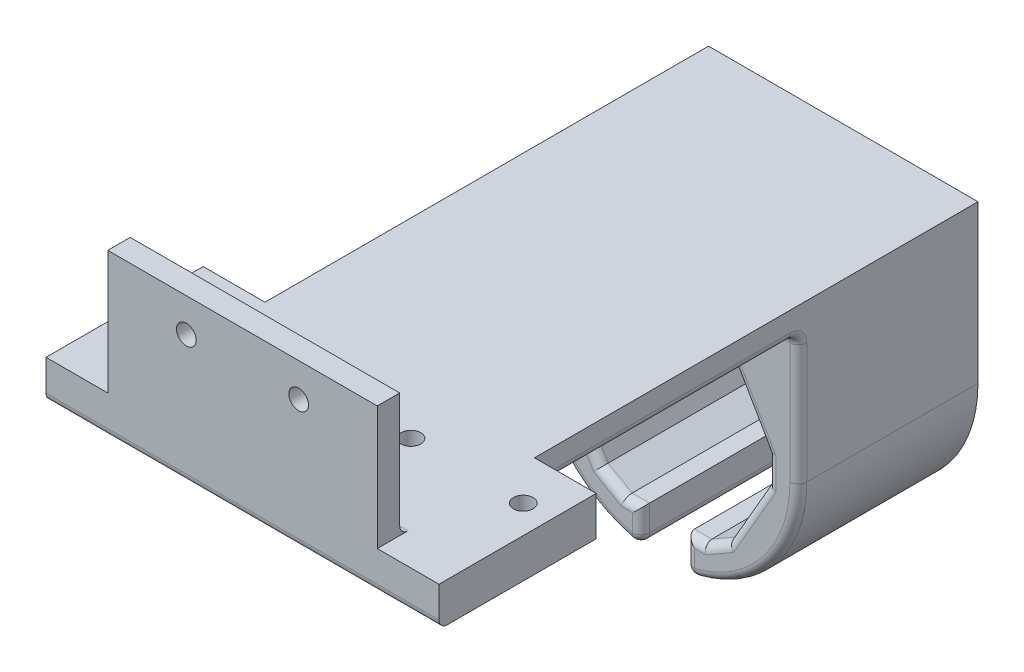
SolidWorks part; units mm, degrees
ref_plane "Front Plane" through (0, 0, 0) normal (1, 0, 0) x (0, 1, 0)
ref_plane "Top Plane" through (0, 0, 0) normal (0, 0, 1) x (0, 1, 0)
ref_plane "Right Plane" through (0, 0, 0) normal (0, 1, 0) x (-1, 0, 0)
sketch "Sketch1" plane through (0, 0, 0) normal (0, 0, 1) x (0, 1, 0)
  circle A0 centre (0, 0) radius 24
  dimension "D1" = 48
extrude "Boss-Extrude2" add sketch "Sketch1" along normal blind 32
sketch "Sketch2" plane through (0, 0, 32) normal (0, 0, 1) x (1, 0, 0)
  line L0 (0, 0) -> (-19.9053, 0) construction
  line L1 (7.1, 17.2385) -> (-7.0999, 17.2385)
  line L2 (-11.379, 14.768) -> (-18.4789, 2.4705)
  line L3 (-18.4789, -2.4705) -> (-11.379, -14.768)
  line L4 (-7.0999, -17.2385) -> (7.1, -17.2385)
  line L5 (11.379, -14.768) -> (18.479, -2.4705)
  line L6 (18.479, 2.4705) -> (11.379, 14.768)
  line L7 (-7.0999, 17.2385) -> (-11.379, 14.768)
  line L8 (11.379, 14.768) -> (7.1, 17.2385)
  line L9 (18.479, -2.4705) -> (18.479, 2.4705)
  line L10 (7.1, -17.2385) -> (11.379, -14.768)
  line L11 (-11.379, -14.768) -> (-7.0999, -17.2385)
  line L12 (-18.4789, 2.4705) -> (-18.4789, -2.4705)
  circle A0 centre (0, 0) radius 17.2385 construction
  point P2 (9.9527, 17.2385)
  point P3 (-9.9526, 17.2385)
  point P5 (-9.9526, -17.2385)
  point P6 (9.9527, -17.2385)
  point P7 (19.9053, 0)
  dimension "D1" = 19.9053
extrude "Cut-Extrude1" cut sketch "Sketch2" against normal blind 28
sketch "Sketch3" plane through (0, 0, 0) normal (0, 0, -1) x (1, 0, 0)
  line L1 (-4, -4) -> (4, -4)
  line L2 (-4, -4) -> (-4, 4)
  line L3 (-4, 4) -> (4, 4)
  line L4 (4, -4) -> (4, 4)
  line L5 (-4, -4) -> (4, 4) construction
  line L6 (-4, 4) -> (4, -4) construction
  point P0 (0, 0)
  dimension "D1" = 8
extrude "Cut-Extrude2" cut sketch "Sketch3" against normal up to next
sketch "Sketch4" plane through (0, 0, 32) normal (0, 0, 1) x (1, 0, 0)
  line L0 (-24, 0) -> (-24, 28)
  line L1 (-24, 28) -> (24, 28)
  line L2 (24, 28) -> (24, 0)
  line L3 (-24, 0) -> (-22, 0)
  line L4 (22, 0) -> (24, 0)
  circle A0 centre (0, 0) radius 24 construction
  arc A2 (-22, 0) -> (22, 0) centre (0, 0) cw
  point P11 (0, 0)
  dimension "D1" = 2
  dimension "D2" = 28
extrude "Boss-Extrude3" add sketch "Sketch4" against normal up to surface (32 mm away) up to face at (0, 0, 0)
sketch "Sketch6" plane through (0, 0, 32) normal (0, 0, 1) x (1, 0, 0)
  line L0 (24, 0) -> (24, 28) construction
  line L1 (-24, 28) -> (24, 28)
  line L2 (-24, 28) -> (-24, 23)
  line L3 (-24, 23) -> (24, 23)
  line L4 (24, 28) -> (24, 23)
  dimension "D1" = 5
extrude "Boss-Extrude4" add sketch "Sketch6" along normal blind 75
sketch "Sketch7" plane through (0, 28, 0) normal (0, 1, 0) x (-1, 0, 0)
  line L0 (24, 0) -> (24, 107) construction
  line L1 (-24, 107) -> (24, 107)
  line L2 (-24, 107) -> (-24, 103)
  line L3 (-24, 103) -> (24, 103)
  line L4 (24, 107) -> (24, 103)
  dimension "3" = 4
extrude "Boss-Extrude5" add sketch "Sketch7" along normal blind 22
sketch "Sketch8" plane through (0, 0, 103) normal (0, 0, -1) x (1, 0, 0)
  line L0 (24, -50) -> (-24, -50) construction
  line L1 (0, -50) -> (0, -28) construction
  line L2 (24, -28) -> (-24, -28) construction
  line L3 (0, -44) -> (-24, -44) construction
  line L4 (-24, -50) -> (-24, -28) construction
  line L5 (-24, -28) -> (24, -28) construction
  circle A1 centre (-10, -44) radius 1.75
  circle A2 centre (10, -44) radius 1.75
  dimension "D1" = 3.5
  dimension "D2" = 10
  dimension "D3" = 16
extrude "Cut-Extrude3" cut sketch "Sketch8" against normal up to next
sketch "Sketch9" plane through (0, 28, 0) normal (0, 1, 0) x (-1, 0, 0)
  line L0 (0, 103) -> (0, 0) construction
  line L1 (-24, 103) -> (24, 103) construction
  line L2 (0, 87) -> (-24, 87) construction
  line L3 (-24, 0) -> (-24, 103) construction
  line L4 (-24, 103) -> (24, 103) construction
  circle A1 centre (-20, 87) radius 1.85
  circle A2 centre (20, 87) radius 1.85
  dimension "D1" = 16
  dimension "D2" = 20
extrude "Cut-Extrude4" [suppressed] cut sketch "Sketch9" against normal up to next
sketch "Sketch11" plane through (0, 23, 0) normal (0, -1, 0) x (1, 0, 0)
  line L0 (-24, 107) -> (24, 107) construction
  line L1 (-35, 107) -> (35, 107)
  line L2 (-35, 107) -> (-35, 79)
  line L3 (-35, 79) -> (35, 79)
  line L4 (35, 107) -> (35, 79)
  line L5 (0, 0) -> (0, 107) construction
  dimension "D1" = 28
  dimension "D2" = 70
extrude "Boss-Extrude7" add sketch "Sketch11" against normal blind 5 and the other way blind 2
sketch "Sketch12" plane through (0, 28, 0) normal (0, 1, 0) x (-1, 0, 0)
  line L0 (0, 103) -> (0, 107) construction
  line L1 (-24, 103) -> (24, 103) construction
  line L2 (24, 107) -> (-24, 107) construction
  line L3 (-35, 87) -> (35, 87) construction
  line L4 (-35, 79) -> (-35, 107) construction
  line L5 (35, 107) -> (35, 79) construction
  line L6 (-24, 103) -> (24, 103) construction
  circle A0 centre (-10, 87) radius 1.75
  circle A1 centre (-30, 87) radius 1.75
  circle A2 centre (10, 87) radius 1.75
  circle A3 centre (30, 87) radius 1.75
  dimension "D4" = 3.5
  dimension "D1" = 16
  dimension "D2" = 20
  dimension "D3" = 10
extrude "Cut-Extrude5" cut sketch "Sketch12" against normal up to next
sketch "Sketch13" plane through (0, 0, 32) normal (0, 0, 1) x (1, 0, 0)
  line L0 (-4, -4) -> (-4, -23.6643)
  line L1 (-4, -4) -> (4, -4)
  line L2 (4, -4) -> (4, -23.6643)
  line L3 (4, -4) -> (-4, -4) construction
  line L4 (-4, -4) -> (-4, 4) construction
  line L5 (4, 4) -> (4, -4) construction
  arc A0 (-24, 0) -> (24, 0) centre (0, 0) ccw construction
  arc A1 (4, -23.6643) -> (-4, -23.6643) centre (0, 0) cw
extrude "Cut-Extrude6" cut sketch "Sketch13" against normal through all
fillet "Fillet2" radius 1.5 26 edges at (0, 23, 32) (0, 21, 107) (0, 28, 103) (-24, 23, 55.5) (24, 23, 55.5) (9.2395, -16.0032, 32) (14.929, -8.6192, 32) (18.479, 0, 32) (14.929, 8.6192, 32) (9.2395, 16.0032, 32) (0, 17.2385, 32) (-9.2395, 16.0032, 32) (-14.929, 8.6192, 32) (-18.4789, 0, 32) (-14.929, -8.6192, 32) (-9.2395, -16.0032, 32) (-4, -20.4514, 32) (-18.3303, -15.4919, 32) (-24, 11.5, 32) (24, 11.5, 32) (18.3303, -15.4919, 32) (4, -20.4514, 32) (4, -23.6643, 16) (-4, -23.6643, 16) (5.55, -17.2385, 32) (-5.55, -17.2385, 32)
fillet "Fillet3" radius 4 2 edges at (-4, 4, 2) (4, 4, 2)
